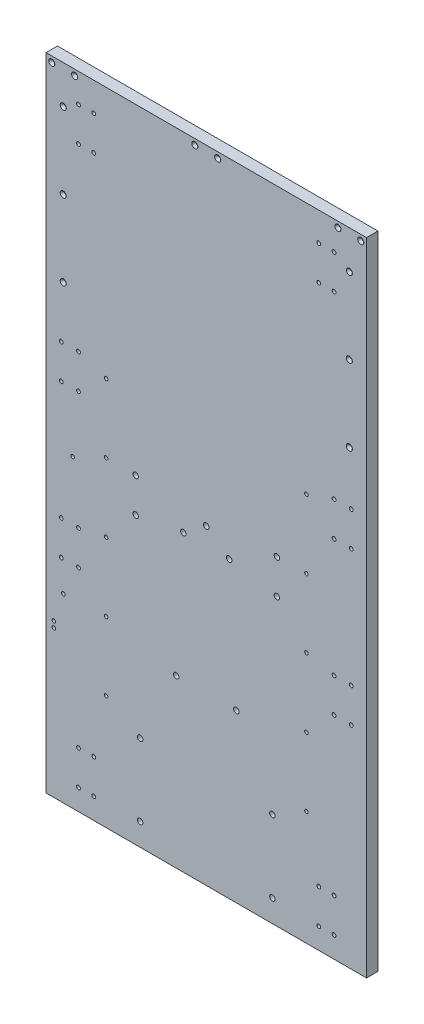
SolidWorks part; units mm, degrees
material "Beech"
ref_plane "Front Plane" through (0, 0, 0) normal (0, 0, 1) x (1, 0, 0)
ref_plane "Top Plane" through (0, 0, 0) normal (0, 1, 0) x (1, 0, 0)
ref_plane "Right Plane" through (0, 0, 0) normal (1, 0, 0) x (0, 0, -1)
sketch "Sketch1" plane through (0, 0, 0) normal (0, 0, 1) x (1, 0, 0)
  line L8 (266.573, 7002.78) -> (-266.573, 7002.78)
  line L9 (-266.573, 7002.78) -> (-266.573, 5935.98)
  line L10 (-266.573, 5935.98) -> (266.573, 5935.98)
  line L11 (266.573, 5935.98) -> (266.573, 7002.78)
  point P2 (0, 7002.78)
  dimension "D1" = 1066.8
  dimension "D2" = 533.146
extrude "Boss-Extrude1" add sketch "Sketch1" against normal blind 19.05
hole_wizard "23/64 (0.35938) Diameter Hole1" positions "Sketch2" profile "Sketch3" hole size "23/64" standard "ANSI Inch" end condition through all
sketch "Sketch2" plane through (0, 0, -19.05) normal (0, 0, -1) x (-1, 0, 0)
  point P15 (110, 5973.262)
  point P18 (110, 6093.262)
  point P21 (-110, 6093.262)
  point P24 (-110, 5973.262)
  point P27 (-50, 6213.262)
  point P30 (50, 6213.262)
  point P33 (-117.475, 6411.087)
  point P36 (-117.475, 6468.237)
  point P39 (117.475, 6411.087)
  point P42 (117.475, 6468.237)
  point P55 (-38.1, 6425.3745)
  point P58 (0, 6453.9495)
  point P61 (38.1, 6425.3745)
sketch "Sketch3" plane through (-110, 5973.262, -19.05) normal (1, 0, 0) x (0, 1, 0)
  line L0 (0, 0) -> (0, 19.05)
  line L1 (0, 19.05) -> (4.5641, 19.05)
  line L2 (4.5641, 19.05) -> (4.5641, 0)
  line L5 (4.5641, 0) -> (0, 0)
  line L11 (0, -6.35) -> (0, 107.95) construction
  dimension "Thru Hole Dia." = 9.1283
  dimension "Thru Hole Depth" = 19.05
sketch "Sketch4" plane through (0, 0, 0) normal (0, 0, 1) x (1, 0, 0)
  line L0 (-266.573, 7002.78) -> (-266.573, 5935.98) construction
  line L1 (-266.573, 5935.98) -> (-222.123, 5935.98)
  line L2 (-266.573, 5935.98) -> (-266.573, 6012.18)
  line L3 (-266.573, 6012.18) -> (-222.123, 6012.18)
  line L4 (-222.123, 5935.98) -> (-222.123, 6012.18)
  line L5 (-266.573, 7002.78) -> (-222.123, 7002.78)
  line L6 (-266.573, 7002.78) -> (-266.573, 6926.58)
  line L7 (-266.573, 6926.58) -> (-222.123, 6926.58)
  line L8 (-222.123, 7002.78) -> (-222.123, 6926.58)
  line L9 (266.573, 7002.78) -> (-266.573, 7002.78) construction
  line L10 (266.573, 5935.98) -> (266.573, 7002.78) construction
  line L11 (266.573, 7002.78) -> (222.123, 7002.78)
  line L12 (266.573, 7002.78) -> (266.573, 6926.58)
  line L13 (266.573, 6926.58) -> (222.123, 6926.58)
  line L14 (222.123, 7002.78) -> (222.123, 6926.58)
  line L15 (-266.573, 5935.98) -> (266.573, 5935.98) construction
  line L16 (266.573, 5935.98) -> (222.123, 5935.98)
  line L17 (266.573, 5935.98) -> (266.573, 6012.18)
  line L18 (266.573, 6012.18) -> (222.123, 6012.18)
  line L19 (222.123, 5935.98) -> (222.123, 6012.18)
  dimension "D1" = 76.2
  dimension "D2" = 44.45
split line "Split Line1" [suppressed]
hole_wizard "15/64 (0.23438) Diameter Hole1" positions "Sketch5" profile "Sketch6" hole size "15/64" standard "ANSI Inch" end condition through all
sketch "Sketch5" plane through (0, 0, -19.05) normal (0, 0, -1) x (-1, 0, 0)
  point P0 (166.6875, 6125.8958)
  point P2 (166.6875, 6240.1958)
  point P4 (166.6875, 6354.4958)
  point P6 (166.6875, 6468.7958)
  point P8 (166.6875, 6583.0958)
  point P14 (-166.6875, 6125.8958)
  point P16 (-166.6875, 6240.1958)
  point P18 (-166.6875, 6354.4958)
  point P20 (-166.6875, 6468.7958)
  point P22 (-166.6875, 6583.0958)
sketch "Sketch6" plane through (-166.6875, 6125.8958, -19.05) normal (1, 0, 0) x (0, 1, 0)
  line L0 (0, 0) -> (0, 19.05)
  line L1 (0, 19.05) -> (2.9766, 19.05)
  line L2 (2.9766, 19.05) -> (2.9766, 0)
  line L5 (2.9766, 0) -> (0, 0)
  line L11 (0, -6.35) -> (0, 107.95) construction
  dimension "Thru Hole Dia." = 5.9533
  dimension "Thru Hole Depth" = 19.05
hole_wizard "1/4 (0.25) Diameter Hole1" positions "Sketch9" profile "Sketch10" hole size "1/4" standard "ANSI Inch" end condition through all
sketch "Sketch9" plane through (0, 0, 0) normal (0, 0, 1) x (1, 0, 0)
  line L0 (0, 7002.78) -> (0, 5935.98) construction
  line L1 (-266.573, 5935.98) -> (266.573, 5935.98) construction
  point P0 (-212.598, 6955.155)
  point P2 (-212.598, 6898.005)
  point P4 (-187.198, 6898.005)
  point P6 (-187.198, 6955.155)
  point P12 (-241.173, 6598.9708)
  point P14 (-241.173, 6541.8208)
  point P16 (-212.598, 6541.8208)
  point P18 (-212.598, 6598.9708)
  point P24 (-212.598, 6344.9708)
  point P26 (-241.173, 6344.9708)
  point P28 (-241.173, 6287.8208)
  point P30 (-212.598, 6287.8208)
  point P36 (-212.598, 6028.055)
  point P38 (-187.198, 6028.055)
  point P40 (-187.198, 5970.905)
  point P42 (-212.598, 5970.905)
  point P55 (212.598, 5970.905)
  point P56 (187.198, 5970.905)
  point P57 (187.198, 6028.055)
  point P58 (212.598, 6028.055)
  point P59 (212.598, 6287.8208)
  point P60 (241.173, 6287.8208)
  point P61 (241.173, 6344.9708)
  point P62 (212.598, 6344.9708)
  point P63 (212.598, 6598.9708)
  point P64 (212.598, 6541.8208)
  point P65 (241.173, 6541.8208)
  point P66 (241.173, 6598.9708)
  point P67 (187.198, 6955.155)
  point P68 (187.198, 6898.005)
  point P69 (212.598, 6898.005)
  point P70 (212.598, 6955.155)
sketch "Sketch10" plane through (-212.598, 6955.155, 0) normal (1, 0, 0) x (0, -1, 0)
  line L0 (0, 0) -> (0, 19.05)
  line L1 (0, 19.05) -> (3.175, 19.05)
  line L2 (3.175, 19.05) -> (3.175, 0)
  line L5 (3.175, 0) -> (0, 0)
  line L11 (0, -6.35) -> (0, 107.95) construction
  dimension "Thru Hole Dia." = 6.35
  dimension "Thru Hole Depth" = 19.05
hole_wizard "15/64 (0.23438) Diameter Hole2" positions "Sketch11" profile "Sketch12" hole size "15/64" standard "ANSI Inch" end condition through all
sketch "Sketch11" plane through (0, 0, -19.05) normal (0, 0, -1) x (-1, 0, 0)
  line L0 (252.423, 6180.33) -> (255.223, 6180.33) construction
  line L2 (252.423, 6190.33) -> (255.223, 6190.33) construction
  line L3 (266.573, 5935.98) -> (-266.573, 5935.98) construction
  line L4 (266.573, 7002.78) -> (266.573, 5935.98) construction
  point P11 (253.823, 6180.33)
  point P13 (253.823, 6190.33)
  point P14 (237.948, 6237.3129)
  point P16 (222.123, 6442.7873)
  dimension "D1" = 206.0829
  dimension "D2" = 301.3329
  dimension "D3" = 28.625
  dimension "D4" = 44.45
sketch "Sketch12" plane through (-222.123, 6442.7873, -19.05) normal (1, 0, 0) x (0, 1, 0)
  line L0 (0, 0) -> (0, 19.05)
  line L1 (0, 19.05) -> (2.9766, 19.05)
  line L2 (2.9766, 19.05) -> (2.9766, 0)
  line L5 (2.9766, 0) -> (0, 0)
  line L11 (0, -6.35) -> (0, 107.95) construction
  dimension "Thru Hole Dia." = 5.9533
  dimension "Thru Hole Depth" = 19.05
hole_wizard "Hole1" positions "Sketch13" profile "Sketch14" legacy
sketch "Sketch13" plane through (0, 0, 0) normal (0, 0, 1) x (1, 0, 0)
  line L0 (0, 7002.78) -> (0, 5935.98) construction
  line L4 (237.998, 7002.78) -> (237.998, 5935.98) construction
  line L8 (266.573, 6993.255) -> (0, 6993.255) construction
  line L12 (237.998, 6939.28) -> (237.998, 6686.1919)
  point P26 (237.998, 6686.1919)
  point P27 (257.048, 6993.255)
  point P29 (218.948, 6993.255)
  point P31 (19.05, 6993.255)
  point P35 (237.998, 6939.28)
  point P42 (237.998, 6812.7359)
  point P51 (-237.998, 6812.7359)
  point P52 (-237.998, 6939.28)
  point P53 (-19.05, 6993.255)
  point P54 (-218.948, 6993.255)
  point P55 (-257.048, 6993.255)
  point P56 (-237.998, 6686.1919)
sketch "Sketch14" plane through (-237.998, 6686.1919, 0) normal (1, 0, 0) x (0, -1, 0)
  line L0 (0, 0) -> (0, 39.0539)
  line L1 (0, 39.0539) -> (1.5875, 38.1)
  line L2 (1.5875, 38.1) -> (1.5875, 4.0177)
  line L3 (1.5875, 4.0177) -> (5.08, 0)
  line L4 (5.08, 0) -> (0, 0)
  line L5 (0, -14.3089) -> (0, 102.4216) construction
  line L6 (0, 39.0539) -> (-1.5875, 38.1) construction
  line L7 (-1.5875, 4.0177) -> (-5.08, 0) construction
  dimension "Diameter" = 3.175
  dimension "Depth" = 38.1
  dimension "C-Sink Diameter" = 10.16
  dimension "C-Sink Angle" = 82
  dimension "Drill Angle" = 118
